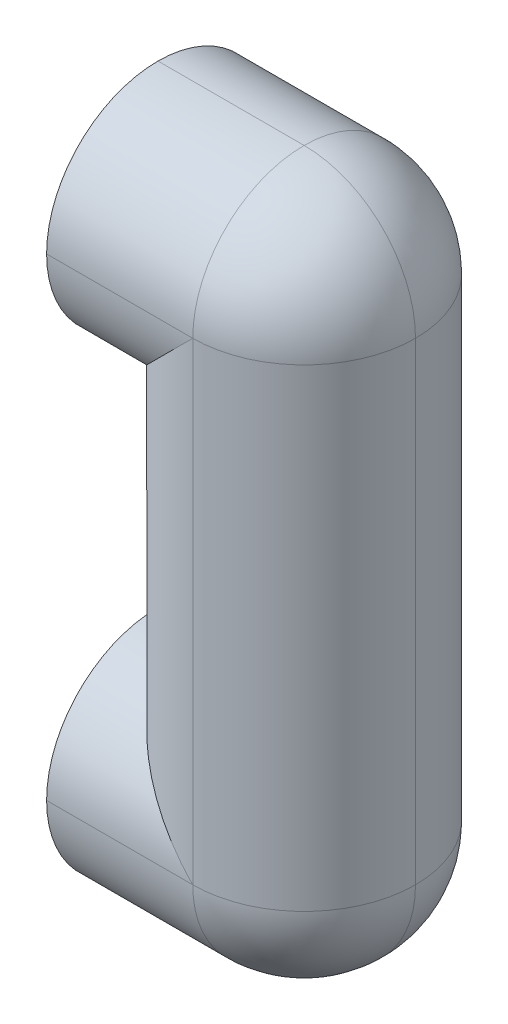
SolidWorks part; units mm, degrees
ref_plane "Front Plane" through (0, 0, 0) normal (0, 0, 1) x (1, 0, 0)
ref_plane "Top Plane" through (0, 0, 0) normal (0, 1, 0) x (1, 0, 0)
ref_plane "Right Plane" through (0, 0, 0) normal (1, 0, 0) x (0, 0, -1)
sketch "Sketch1" plane through (0, 0, 0) normal (0, 1, 0) x (1, 0, 0)
  line L1 (0, 0) -> (48, 0)
  line L2 (0, 0) -> (0, 48)
  line L3 (0, 48) -> (48, 48)
  line L4 (48, 0) -> (48, 48)
  dimension "D1" = 48
  dimension "D2" = 48
extrude "Boss-Extrude1" add sketch "Sketch1" along normal mid plane 150
sketch "Sketch2" plane through (0, 0, 0) normal (-1, 0, 0) x (0, 0, 1)
  line L0 (0, 75) -> (0, -75) construction
  line L1 (-48, 75) -> (0, 75)
  line L2 (-48, 75) -> (-48, 27)
  line L3 (-48, 27) -> (0, 27)
  line L4 (0, 75) -> (0, 27)
  line L6 (-48, -75) -> (0, -75)
  line L7 (-48, -75) -> (-48, -27)
  line L8 (-48, -27) -> (0, -27)
  line L9 (0, -75) -> (0, -27)
  dimension "D1" = 48
  dimension "D2" = 48
extrude "Boss-Extrude2" add sketch "Sketch2" along normal mid plane 15
fillet "Fillet1" radius 24 12 edges at (48, 0, 0) (48, 0, -48) (20.25, -75, -48) (20.25, -75, 0) (-3.75, -27, 0) (-3.75, -27, -48) (0, 0, 0) (0, 0, -48) (-3.75, 27, 0) (-3.75, 27, -48) (20.25, 75, -48) (20.25, 75, 0)
sketch "Sketch3" plane through (-7.5, 0, 0) normal (-1, 0, 0) x (0, 0, 1)
  circle A0 centre (-24, -51) radius 5
  dimension "D1" = 10
extrude "Cut-Extrude1" cut sketch "Sketch3" against normal blind 15
sketch "Sketch4" plane through (-7.5, 0, 0) normal (-1, 0, 0) x (0, 0, 1)
  circle A0 centre (-24, 51) radius 5
  dimension "D1" = 10
extrude "Boss-Extrude3" add sketch "Sketch4" along normal mid plane 15
